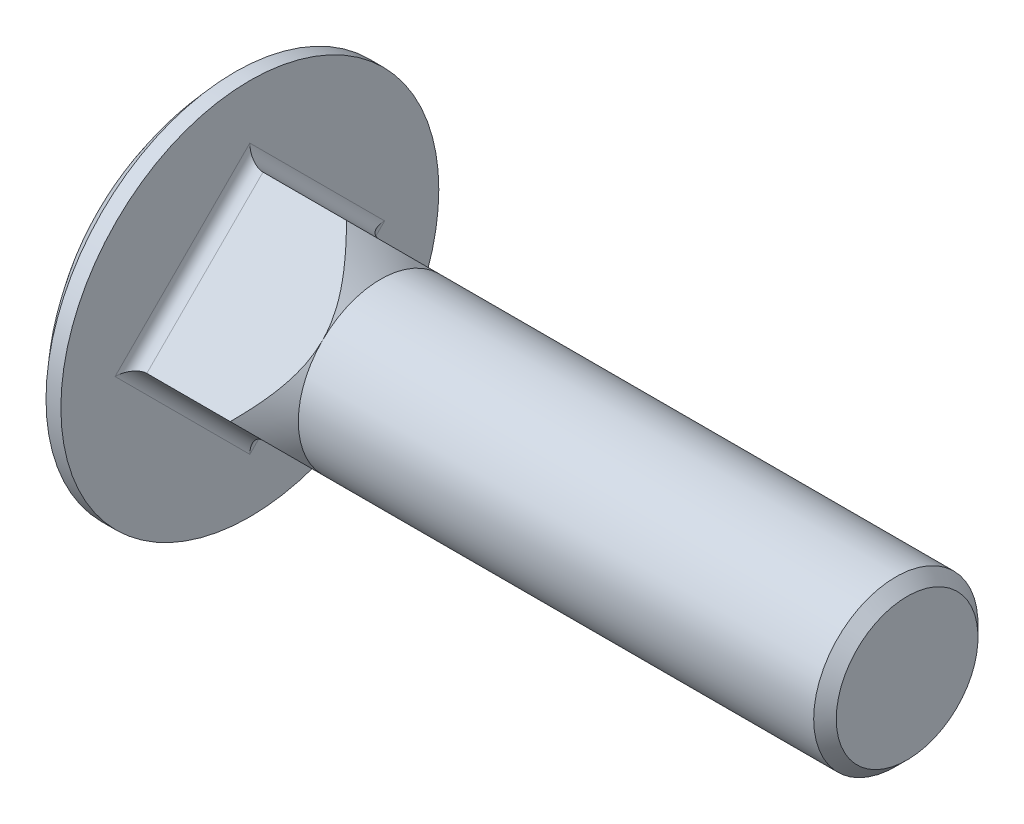
SolidWorks part; units mm, degrees
revolve "Base-Revolve" add sketch "BodySke" angle 360 about L6 other way angle 60
sketch "BodySke" plane through (0, 0, 0) normal (0, 0, 1) x (1, 0, 0)
  line L1 (9.0906, 23) -> (10.9, 23)
  line L2 (10.9, 23) -> (10.9, 10)
  line L3 (10.9, 10) -> (89.526, 10)
  line L4 (90.9, 8.626) -> (90.9, 0)
  line L5 (90.9, 0) -> (0, 0)
  line L6 (-31.75, 0) -> (127, 0) construction
  line L8 (90.9, 8.626) -> (89.526, 10)
  line L10 (90.9, -8.626) -> (89.526, -10) construction
  line L11 (13.4, 7.799) -> (13.4, 1.449) construction
  line L12 (30.9, 7.799) -> (30.9, 1.449) construction
  line L13 (30.9, 7.799) -> (30.9, 1.449) construction
  arc A0 (9.0906, 23) -> (0, 0) centre (33.6413, 0) ccw
  dimension "Diameter" = 20
  dimension "Head_dia" = 46
  dimension "Head_ht" = 10.9
  dimension "D1" = 1.8094
  dimension "Thread_length" = 60
cosmetic thread "ThreadCosmetic" [suppressed] parameters "Thread_length"=60, "Thread_minor"=17.252
ref_plane "Plane1" through (0, 0, 0) normal (0, 0, 1) x (1, 0, 0)
ref_plane "Plane2" through (0, 0, 0) normal (0, 1, 0) x (1, 0, 0)
ref_plane "Plane3" through (0, 0, 0) normal (1, 0, 0) x (0, 0, -1)
sketch "Sketch1" plane through (10.9, 0, 0) normal (1, 0, 0) x (0, 0, -1)
  line L0 (0, 14.1421) -> (14.1421, 0)
  line L1 (14.1421, 0) -> (0, -14.1421)
  line L2 (0, -14.1421) -> (-14.1421, 0)
  line L3 (-14.1421, 0) -> (0, 14.1421)
  circle A0 centre (0, 0) radius 10 construction
  circle A1 centre (0, 0) radius 23 construction
  dimension "D1" = 20
extrude "Boss-Extrude1" add sketch "Sketch1" along normal blind 15.9
sketch "Sketch2" plane through (0, 0, 0) normal (0, 0, 1) x (1, 0, 0)
  line L0 (0, 0) -> (101.6, 0) construction
  line L1 (26.8, 10) -> (31.8, 10)
  line L2 (26.8, 10) -> (12.8, 24)
  line L3 (31.8, 10) -> (31.8, 24)
  line L4 (31.8, 24) -> (12.8, 24)
  dimension "D1" = 20
  dimension "D2" = 26.8
  dimension "D3" = 48
  dimension "D4" = 5
  dimension "D5" = 45
revolve "Cut-Revolve1" cut sketch "Sketch2" angle 360 about L0
fillet "Fillet1" radius 1.6 4 edges at (10.9, 7.0711, 7.0711) (10.9, -7.0711, 7.0711) (10.9, -7.0711, -7.0711) (10.9, 7.0711, -7.0711)
sketch "ThdSchSke" plane through (0, 0, 0) normal (0, 0, 1) x (1, 0, 0)
  line L0 (30.9, -8.626) -> (29.9379, -10)
  line L1 (30.9, -8.626) -> (31.8621, -10)
  line L2 (31.8621, -10) -> (31.8621, -12.5)
  line L3 (0, 0) -> (5.1513, 0) construction
  line L5 (31.8621, -12.5) -> (29.9379, -12.5)
  line L6 (29.9379, -12.5) -> (29.9379, -10)
  arc A0 (9.0906, 23) -> (9.0906, -23) centre (33.6413, 0) ccw construction
  dimension "Diameter" = 20
  dimension "Thread_minor" = 17.252
  dimension "Start" = 30.9
revolve "ThreadSchematic" [suppressed] cut sketch "ThdSchSke" angle 360 about L3
pattern_linear "ThdSchPat" [suppressed]
equation "\"Thread_minor@ThreadCosmetic\"  =  \"Minor_dia@BodySke\""
equation "\"Thread_length@ThreadCosmetic\" = ((sgn( (\"Length@BodySke\" - \"Advance@BodySke\" * 3.0) - \"Thread_nom@BodySke\" )-1)*( (\"Length@BodySke\" - \"Advance@BodySke\" * 3.0) - \"Thread_nom@BodySke\" ))/-2+ \"Thread_nom@BodySke\""
equation "\"Thread_minor@ThdSchSke\" = \"Minor_dia@BodySke\""
equation "\"Diameter@ThdSchSke\" = \"Diameter@BodySke\""
equation "\"Overcut@ThdSchSke\" = \"Diameter@BodySke\" * 1.25"
equation "\"Start@ThdSchSke\" = \"Head_ht@BodySke\" + \"Length@BodySke\" - \"Thread_length@ThreadCosmetic\"  '---Non-countersunk---"
equation "\"Num_threads@ThdSchPat\" = int( \"Thread_length@ThreadCosmetic\" / \"Advance@BodySke\" + 0.999 )  + 1"
equation "\"Advance@ThdSchPat\" = \"Thread_length@ThreadCosmetic\" /  (\"Num_threads@ThdSchPat\" - 1) 'relax it"
equation "\"Num_threads@ThdSchPat\" = \"Num_threads@ThdSchPat\" - sgn( \"Num_threads@ThdSchPat\" - 1) '---chamfered tips only---"
equation "\"D1@BodySke\" = \"Head_ht@BodySke\" * .166"
equation "\"D1@Sketch2\" = \"Diameter@BodySke\""
equation "\"D2@Sketch2\" = \"Head_ht@BodySke\" + \"NeckHt@Boss-Extrude1\""
equation "\"D3@Sketch2\" = \"Head_dia@BodySke\" + 2"
equation "\"D1@Sketch1\" = \"Diameter@BodySke\""
